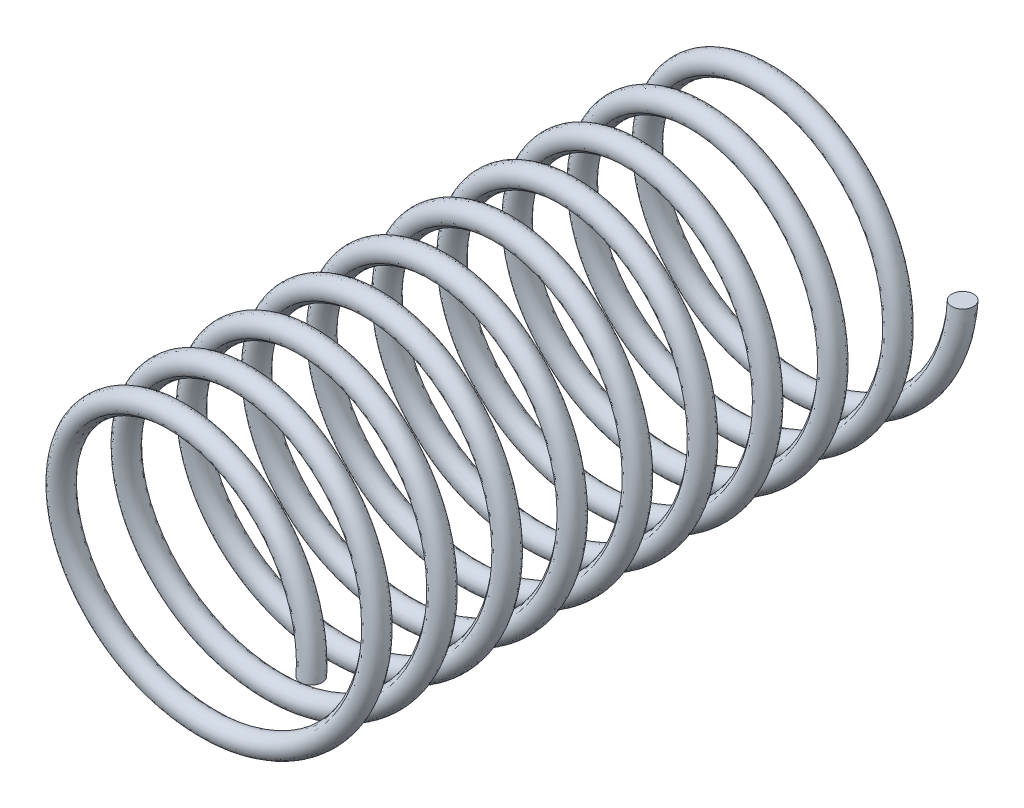
SolidWorks part; units mm, degrees
material "201 Gehärteter Edelstahl (SS)"
ref_plane "xy" through (0, 0, 0) normal (0, 0, 1) x (1, 0, 0)
ref_plane "xz" through (0, 0, 0) normal (0, 1, 0) x (1, 0, 0)
ref_plane "yz" through (0, 0, 0) normal (1, 0, 0) x (0, 0, -1)
ref_axis "x" through (-88.99, 0, 0) along (1, 0, 0)
ref_axis "y" through (0, 55, 0) along (0, -1, 0)
ref_axis "z" through (0, 0, 51.4275) along (0, 0, 1)
sketch "Skizze1" plane through (0, 0, 0) normal (0, 0, 1) x (1, 0, 0)
  circle A0 centre (0, 0) radius 3.25
  dimension "D1" = 6.5
curve "Spirale/Helix1" pitch 1.5 height 15 radius 3.25 left hand yes centre (0, 0, 0) axis (0, 0, 1) start towards (1, 0, 0)
sketch "Skizze2" plane through (0, 0, 0) normal (1, 0, 0) x (0, 0, -1)
  circle A0 centre (0, -3.25) radius 0.25
  dimension "D1" = 0.5
sweep "Austragung1" add profiles "Skizze2" path "Spirale/Helix1"
sketch "Skizze3" plane through (0, 0, 0) normal (0, 1, 0) x (1, 0, 0)
  circle A0 centre (3.25, 0.375) radius 0.25 construction
  circle A1 centre (3.25, 0.375) radius 0.25
sketch3d "3D-Skizze1"
  line L0 (0, 0, 51.4275) -> (0, 0, 229.4075) construction
  spline S0 degree 3 poles (3.25, 0, -0.375) (6.9838, 11.7632, -0.8472) (4.9182, 17.6007, -15.5901) (-3.1742, -3.4695, -18.564) (-0.0713, -6.6583, -13.0324) (-1.9205, -8.1262, -6.4282) (0, 0, -8.0012) knots 0 0 0 0 0.511914 0.667789 0.716598 1 1 1 1
